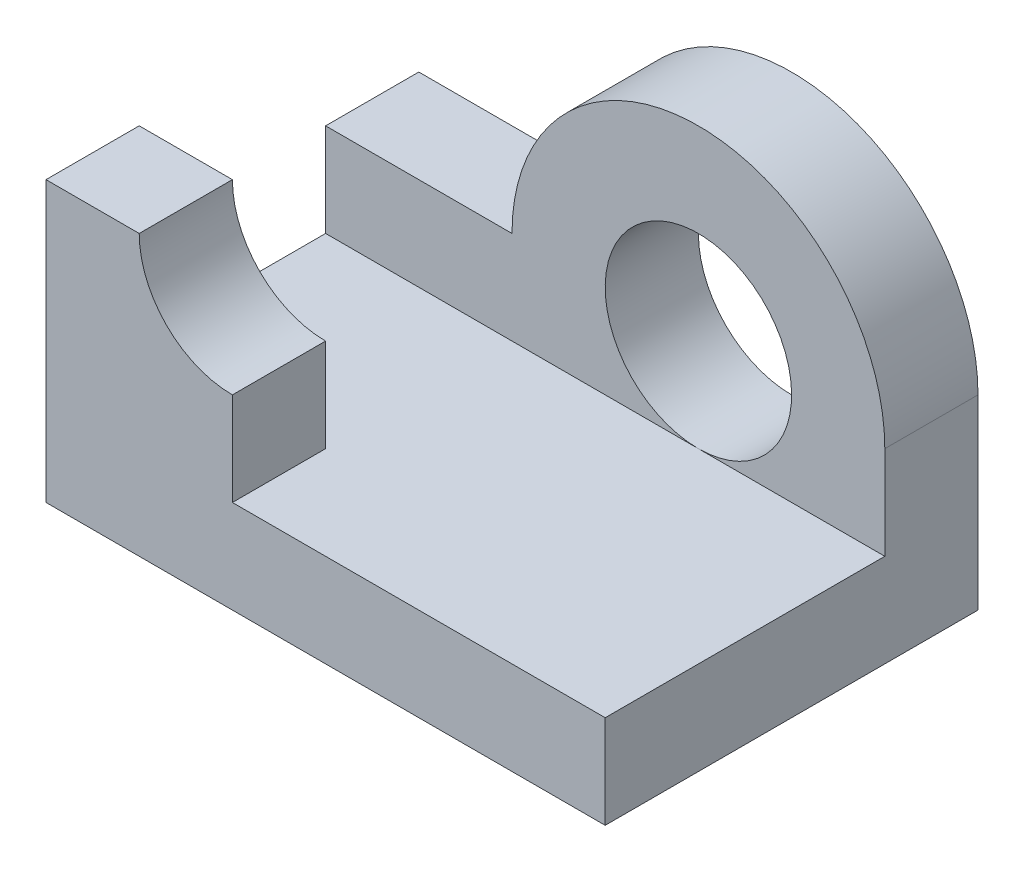
SolidWorks part; units mm, degrees
ref_plane "前基準面" through (0, 0, 0) normal (0, 0, 1) x (1, 0, 0)
ref_plane "上基準面" through (0, 0, 0) normal (0, 1, 0) x (1, 0, 0)
ref_plane "右基準面" through (0, 0, 0) normal (1, 0, 0) x (0, 0, -1)
sketch "草圖1" plane through (0, 0, 0) normal (0, 0, 1) x (1, 0, 0)
  line L0 (10, 0) -> (10, -10)
  line L1 (10, -10) -> (-20, -10)
  line L2 (-10, 0) -> (-10, -5)
  line L3 (-10, -5) -> (-20, -5)
  line L4 (-20, -5) -> (-20, -10)
  circle A0 centre (0, 0) radius 5
  arc A1 (10, 0) -> (-10, 0) centre (0, 0) ccw
  dimension "D1" = 10
  dimension "D2" = 10
  dimension "D3" = 10
  dimension "D4" = 5
  dimension "D5" = 30
extrude "填料-伸長1" add sketch "草圖1" along normal blind 5
sketch "草圖2" plane through (0, 0, 5) normal (0, 0, 1) x (1, 0, 0)
  line L1 (10, -10) -> (10, 0) construction
  line L2 (-20, -10) -> (10, -10)
  line L3 (-20, -10) -> (-20, -5)
  line L4 (-20, -5) -> (10, -5)
  line L5 (10, -10) -> (10, -5)
  dimension "D1" = 5
extrude "填料-伸長3" add sketch "草圖2" along normal blind 15
sketch "草圖3" plane through (0, 0, 20) normal (0, 0, 1) x (1, 0, 0)
  line L1 (-20, -5) -> (-10, -5)
  line L2 (-20, -5) -> (-20, 5)
  line L3 (-20, 5) -> (-15, 5)
  line L4 (-10, -5) -> (-10, 0)
  line L7 (-10, 0) -> (-15, 0)
  line L8 (-15, 5) -> (-15, 0)
  dimension "D1" = 5
  dimension "D2" = 5
  dimension "D3" = 10
  dimension "D4" = 5
extrude "填料-伸長4" add sketch "草圖3" against normal blind 5
fillet "圓角1" radius 5 1 edges at (-15, 0, 17.5)
sketch "草圖4" plane through (-10, 0, 0) normal (-1, 0, 0) x (0, 0, 1)
  line L4 (0, 0) -> (0, -5)
  line L5 (0, -5) -> (5, -5)
  line L6 (5, -5) -> (5, 0)
  line L7 (5, 0) -> (0, 0)
  line L8 (0, 0) -> (0, -5)
  line L9 (0, -5) -> (5, -5)
  line L10 (5, -5) -> (5, 0)
  line L11 (5, 0) -> (0, 0)
  dimension "D1" = 0
extrude "填料-伸長5" add sketch "草圖4" along normal up to surface (10 mm away) up to face at (-20, -3.3333, 11.6667)
